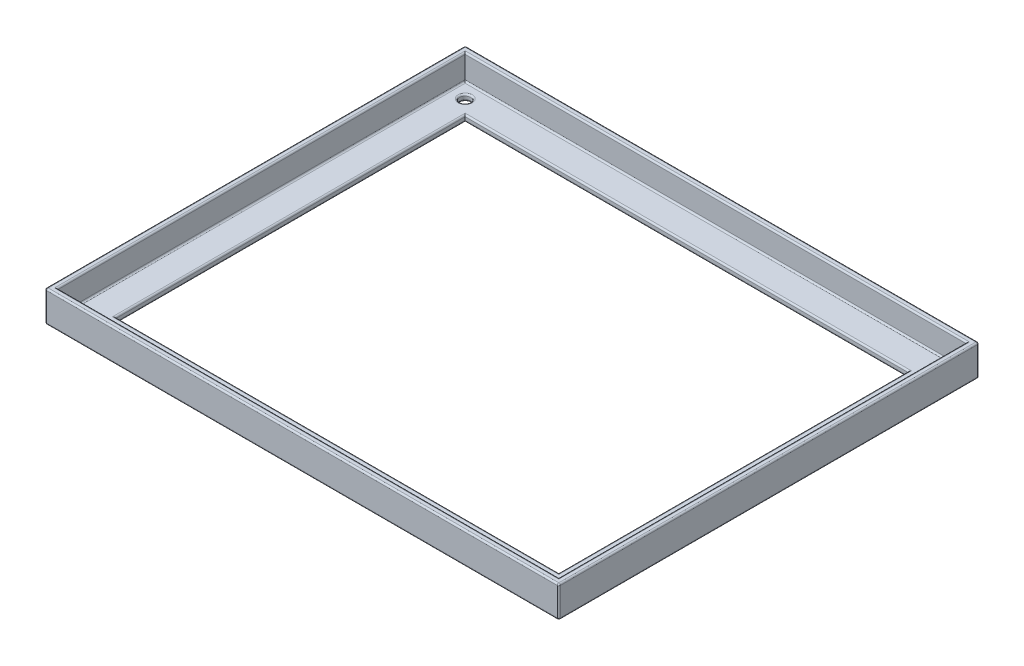
SolidWorks part; units mm, degrees
ref_plane "Front Plane" through (0, 0, 0) normal (0, 0, 1) x (1, 0, 0)
ref_plane "Top Plane" through (0, 0, 0) normal (0, 1, 0) x (1, 0, 0)
ref_plane "Right Plane" through (0, 0, 0) normal (1, 0, 0) x (0, 0, -1)
sketch "Sketch1" plane through (0, 0, 0) normal (0, 1, 0) x (1, 0, 0)
  line L0 (0, 121) -> (9, 121)
  line L3 (0, 130) -> (160, 130)
  line L4 (0, 130) -> (0, 0)
  line L5 (0, 0) -> (160, 0)
  line L6 (160, 130) -> (160, 0)
  line L7 (9, 121) -> (9, 130)
  line L8 (0, 9) -> (9, 9)
  line L9 (9, 9) -> (9, 0)
  line L10 (151, 0) -> (151, 9)
  line L11 (151, 9) -> (160, 9)
  line L12 (160, 121) -> (151, 121)
  line L13 (151, 121) -> (151, 130)
  line L14 (-0.3, 130.3) -> (160.3, 130.3)
  line L15 (9, 121) -> (0, 130) construction
  line L16 (151, 121) -> (160, 130) construction
  line L17 (9, 9) -> (0, 0) construction
  line L18 (151, 9) -> (160, 0) construction
  line L22 (160.3, 130.3) -> (160.3, -0.3)
  line L23 (0, 0) -> (160, 0) construction
  line L24 (0, 0) -> (0, 121) construction
  line L25 (-0.3, -0.3) -> (160.3, -0.3)
  line L26 (-0.3, 130.3) -> (-0.3, -0.3)
  line L27 (-2.3, 132.3) -> (162.3, 132.3)
  line L28 (162.3, 132.3) -> (162.3, -2.3)
  line L29 (-2.3, -2.3) -> (162.3, -2.3)
  line L30 (-2.3, 132.3) -> (-2.3, -2.3)
  line L31 (9, 121) -> (151, 121)
  line L33 (151, 9) -> (151, 121)
  line L35 (151, 9) -> (9, 9)
  line L36 (9, 9) -> (9, 121)
  circle A0 centre (4.5, 125.5) radius 1.75
  circle A1 centre (155.5, 125.5) radius 1.75
  circle A2 centre (155.5, 4.5) radius 1.75
  circle A3 centre (4.5, 4.5) radius 1.75
  dimension "D2" = 3.5
  dimension "D1" = 9
  dimension "D3" = 0.3
  dimension "D4" = 2
  dimension "D9" = 121
  dimension "D11" = 160
extrude "Boss-Extrude1" add sketch "Sketch1" along normal blind 2 contours L8 L36 L0 L4 | L0 L7 L3 L4 A0 | L7 L31 L13 L3 | L13 L12 L6 L3 A1 | L33 L11 L6 L12 | L11 L10 L5 L6 A2 | L10 L35 L9 L5 | L9 L8 L4 L5 A3 | L14 L26 L25 L22 L3 L6 L5 L4 region at (0.1273, 0, -125.5) region at (4.5, 0, -65) region at (80, 0, -125.5) region at (4.5, 0, -8.8727) region at (151.1273, 0, -125.5) region at (155.5, 0, -65) region at (80, 0, -4.5) region at (155.5, 0, -8.8727) region at (80, 0, -130.093)
extrude "Boss-Extrude2" add sketch "Sketch1<3>" along normal blind 10 contours L27 L30 L29 L28 L26 L14 L22 L25 region at (80, 0, -132.0874)
sketch "Sketch1<3>" plane through (0, 0, 0) normal (0, 1, 0) x (1, 0, 0) same geometry as "Sketch1"
fillet "Fillet1" radius 0.5 36 edges at (162.3, 5, -132.3) (162.3, 5, 2.3) (-2.3, 5, -132.3) (-2.3, 5, 2.3) (-2.3, 0, -65) (80, 0, 2.3) (162.3, 0, -65) (80, 0, -132.3) (155.5, 0, -123.75) (155.5, 0, -2.75) (4.5, 0, -2.75) (4.5, 0, -123.75) (151, 0, -65) (80, 0, -9) (9, 0, -65) (80, 0, -121) (162.3, 10, -65) (80, 10, 2.3) (-2.3, 10, -65) (80, 10, -132.3) (80, 10, 0.3) (160.3, 10, -65) (80, 10, -130.3) (-0.3, 10, -65) (155.5, 2, -123.75) (155.5, 2, -2.75) (4.5, 2, -2.75) (4.5, 2, -123.75) (160.3, 2, -65) (80, 2, 0.3) (-0.3, 2, -65) (80, 2, -130.3) (9, 2, -65) (80, 2, -9) (151, 2, -65) (80, 2, -121)
